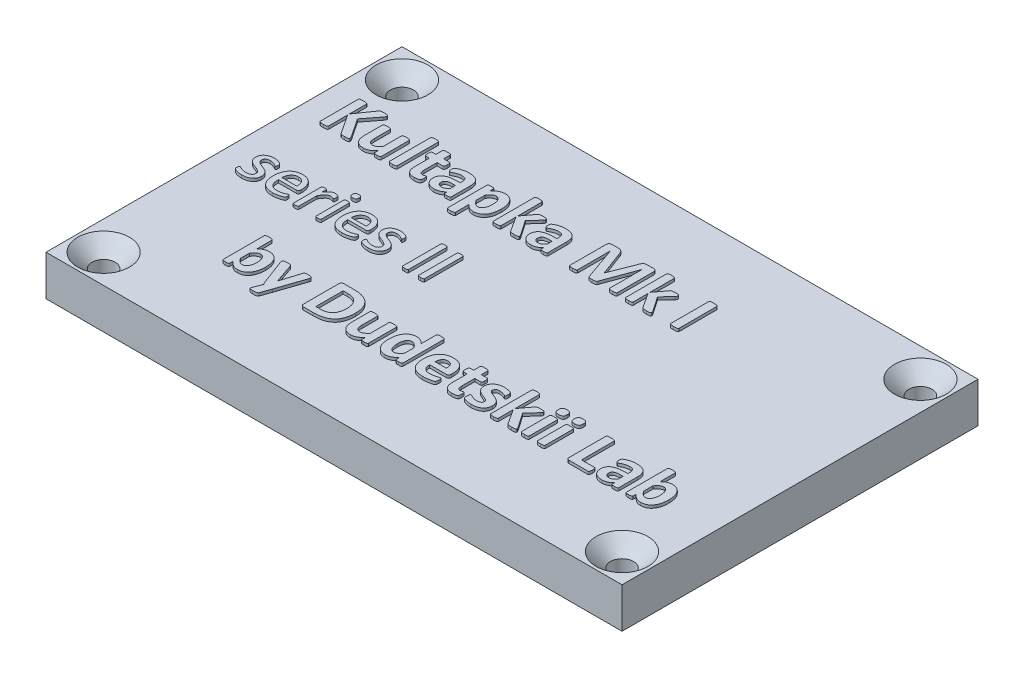
SolidWorks part; units mm, degrees
ref_plane "Спереди" through (0, 0, 0) normal (0, 0, 1) x (1, 0, 0)
ref_plane "Сверху" through (0, 0, 0) normal (0, 1, 0) x (1, 0, 0)
ref_plane "Справа" through (0, 0, 0) normal (1, 0, 0) x (0, 0, -1)
other "Configuration Table"
sketch "Эскиз1" plane through (0, 0, 0) normal (0, 1, 0) x (1, 0, 0)
  line L1 (-46.896, 25.6711) -> (53.104, 25.6711)
  line L2 (-46.896, 25.6711) -> (-46.896, -36.1289)
  line L3 (-46.896, -36.1289) -> (53.104, -36.1289)
  line L4 (53.104, 25.6711) -> (53.104, -36.1289)
  dimension "D1" = 100
  dimension "D2" = 61.8
extrude "Бобышка-Вытянуть1" add sketch "Эскиз1" along normal blind 7
sketch "Эскиз2" plane through (0, 7, 0) normal (0, 1, 0) x (1, 0, 0)
  line L0 (53.104, 25.6711) -> (-46.896, 25.6711) construction
  line L1 (-46.896, -5.2289) -> (53.104, -5.2289) construction
  line L2 (-46.896, 25.6711) -> (-46.896, -36.1289) construction
  line L3 (53.104, -36.1289) -> (53.104, 25.6711) construction
  text T0 "<b>Kultapka Mk I</b>\r\nseries II\r\n<b>     by Dudetskii Lab</b>" font "Calibri" height 7
  dimension "D1" = 19
extrude "Бобышка-Вытянуть2" add sketch "Эскиз2" along normal blind 0.5 separate body
sketch "Эскиз3" plane through (0, 7, 0) normal (0, 1, 0) x (1, 0, 0)
  line L0 (53.104, 25.6711) -> (-46.896, 25.6711) construction
  line L1 (-46.896, 25.6711) -> (-46.896, -36.1289) construction
  line L2 (3.104, 25.6711) -> (3.104, -36.1289) construction
  line L3 (-46.896, -36.1289) -> (53.104, -36.1289) construction
  line L4 (53.104, -5.2289) -> (-46.896, -5.2289) construction
  line L5 (53.104, -36.1289) -> (53.104, 25.6711) construction
  circle A0 centre (-41.896, 20.6711) radius 2
  circle A1 centre (48.104, 20.6711) radius 2
  circle A2 centre (48.104, -31.1289) radius 2
  circle A3 centre (-41.896, -31.1289) radius 2
  dimension "D1" = 5
  dimension "D2" = 5
extrude "Вырез-Вытянуть1" cut sketch "Эскиз3" against normal blind 18.5
chamfer "Фаска1" distance 2.5 angle 45 4 edges at (48.104, 7, -22.6711) (48.104, 7, 33.1289) (-41.896, 7, 29.1289) (-41.896, 7, -18.6711)
